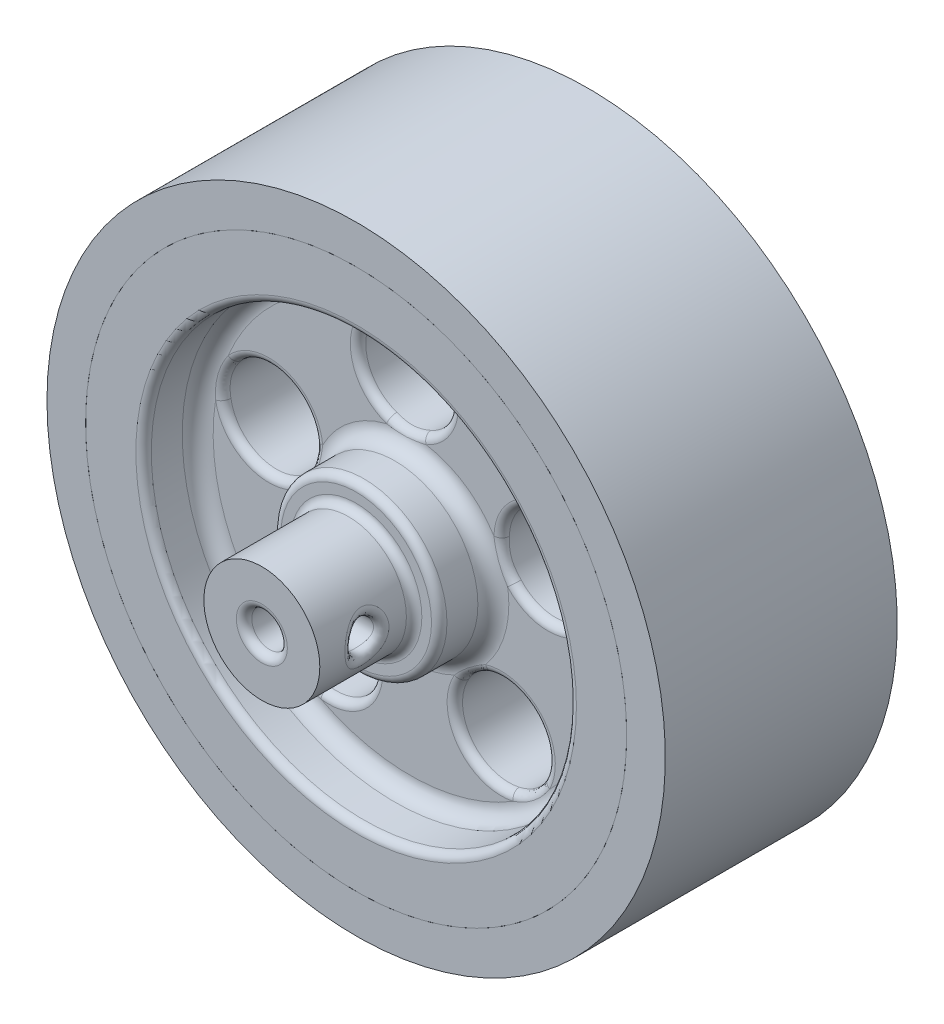
SolidWorks part; units mm, degrees
ref_plane "Front Plane" through (0, 0, 0) normal (0, 0, 1) x (1, 0, 0)
ref_plane "Top Plane" through (0, 0, 0) normal (0, 1, 0) x (1, 0, 0)
ref_plane "Right Plane" through (0, 0, 0) normal (1, 0, 0) x (0, 0, -1)
sketch "Sketch1" plane through (0, 0, 0) normal (0, 0, 1) x (1, 0, 0)
  circle A0 centre (0, 0) radius 35
  dimension "D1" = 70
extrude "Boss-Extrude1" add sketch "Sketch1" along normal blind 30
sketch "Sketch2" plane through (0, 0, 30) normal (0, 0, 1) x (1, 0, 0)
  circle A0 centre (0, 0) radius 10.75
  circle A1 centre (0, 0) radius 27.5
  dimension "D1" = 21.5
extrude "Cut-Extrude1" cut sketch "Sketch2" against normal blind 7
fillet "Fillet3" radius 2 1 edges at (10.75, 0, 23)
fillet "Fillet4" radius 2 1 edges at (27.5, 0, 23)
fillet "Fillet6" radius 1 1 edges at (10.75, 0, 30)
ref_plane "Plane2" through (0, 0, 15) normal (0, 0, 1) x (1, 0, 0)
mirror "Mirror25" about plane through (0, 0, 15) normal (0, 0, 1) of "Cut-Extrude1"
fillet "Fillet7" radius 2 1 edges at (10.75, 0, 7)
fillet "Fillet8" radius 2 1 edges at (27.5, 0, 7)
fillet "Fillet9" radius 1 1 edges at (10.75, 0, 0)
sketch "Sketch3" plane through (0, 0, 30) normal (0, 0, 1) x (1, 0, 0)
  circle A0 centre (0, 0) radius 7.5
  dimension "D1" = 15
extrude "Boss-Extrude2" add sketch "Sketch3" along normal blind 12.2
sketch "Sketch4" plane through (0, 0, 0) normal (0, 0, -1) x (-1, 0, 0)
  circle A0 centre (0, 0) radius 1.6
  dimension "D1" = 3.2
extrude "Cut-Extrude2" cut sketch "Sketch4" against normal blind 2
fillet "Fillet10" radius 1 1 edges at (-1.6, 0, 2)
fillet "Fillet11" radius 1 1 edges at (27.5, 0, 0)
fillet "Fillet12" radius 1 1 edges at (27.5, 0, 30)
sketch "Sketch5" plane through (0, 0, 42.2) normal (0, 0, 1) x (1, 0, 0)
  circle A0 centre (0, 0) radius 2.3
  dimension "D1" = 4.6
extrude "Cut-Extrude3" cut sketch "Sketch5" against normal up to surface (12.2 mm away) up to face at (7.5, 0, 30)
fillet "Fillet14" radius 1 1 edges at (2.3, 0, 42.2)
sketch "Sketch6" plane through (0, 0, 23) normal (0, 0, 1) x (1, 0, 0)
  circle A0 centre (0, 0) radius 19 construction
  circle A1 centre (-0.7508, 18.9852) radius 6
  circle A2 centre (0, 0) radius 19 construction
  circle A3 centre (17.8239, 6.5808) radius 6
  circle A4 centre (0, 0) radius 19 construction
  circle A5 centre (11.7666, -14.918) radius 6
  circle A6 centre (0, 0) radius 19 construction
  circle A7 centre (-10.5518, -15.8006) radius 6
  circle A8 centre (0, 0) radius 19 construction
  circle A9 centre (-18.288, 5.1527) radius 6
  point P19 (0, 0)
  dimension "D1" = 38
  dimension "D2" = 12
  dimension "D3" = 5
extrude "Cut-Extrude6" cut sketch "Sketch6" against normal through all
fillet "Fillet20" radius 1 10 edges at (5.2492, 18.9852, 23) (-6.7508, 18.9852, 7) (-12.288, 5.1527, 23) (-24.288, 5.1527, 7) (-4.5518, -15.8006, 23) (-16.5518, -15.8006, 7) (17.7666, -14.918, 23) (5.7666, -14.918, 7) (23.8239, 6.5808, 23) (11.8239, 6.5808, 7)
sketch "Sketch8" plane through (0, 0, 0) normal (1, 0, 0) x (0, 0, -1)
  line L0 (-42.2, 0) -> (-30, 0) construction
  line L1 (-42.2, 7.5) -> (-42.2, -7.5) construction
  line L2 (-30, 35) -> (-30, -35) construction
  circle A0 centre (-36.1, 0) radius 1.85
  dimension "D1" = 3.7
extrude "Cut-Extrude7" cut sketch "Sketch8" against normal through all both and the other way through all
fillet "Fillet21" radius 1 2 edges at (7.4912, 0.3635, 37.9139) (2.2912, -0.2006, 37.9391)
fillet "Fillet22" radius 1 2 edges at (-7.4912, 0.3635, 34.2861) (-2.2912, 0.2006, 37.9391)
fillet "Fillet23" radius 1 1 edges at (7.5, 0, 30)
sketch "Sketch9" plane through (0, 0, 0) normal (1, 0, 0) x (0, 0, -1)
  line L0 (0, 0) -> (-49.2253, 0) construction
  line L2 (-30, 35) -> (0, 35)
  line L3 (-30, 35) -> (-30, 40)
  line L4 (-30, 40) -> (0, 40)
  line L5 (0, 35) -> (0, 40)
  dimension "D1" = 5
revolve "Revolve1" add sketch "Sketch9" angle 360 about L0
